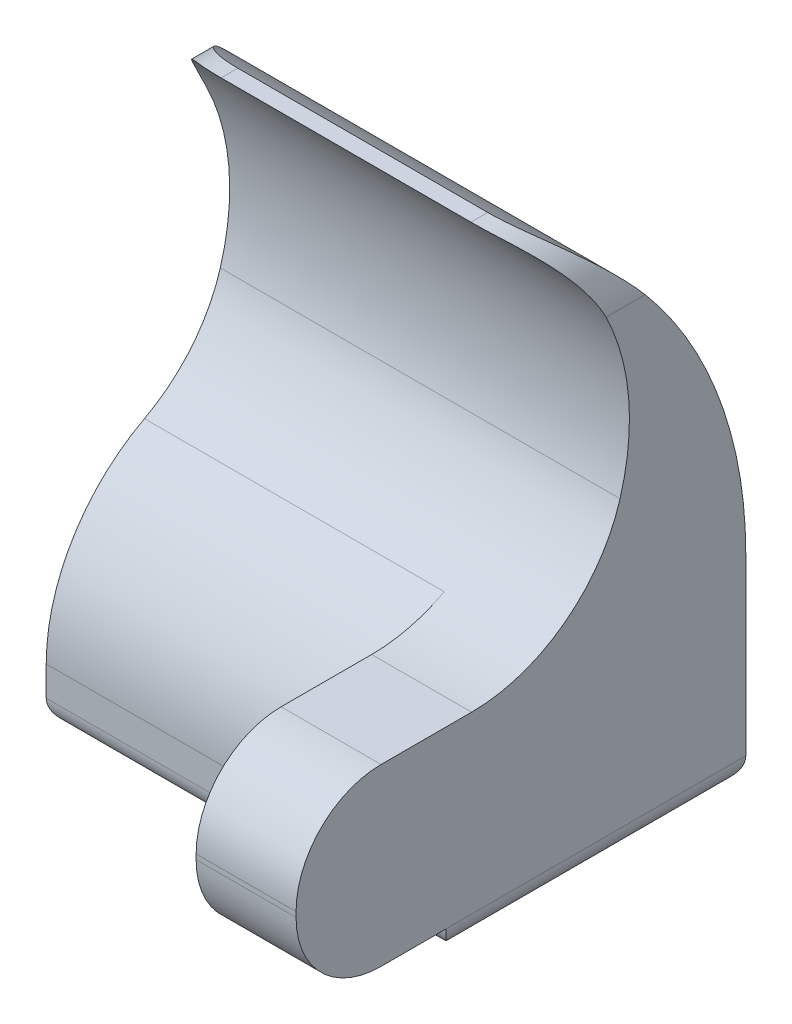
SolidWorks part; units mm, degrees
ref_plane "Front Plane" through (0, 0, 0) normal (0, 0, 1) x (1, 0, 0)
ref_plane "Top Plane" through (0, 0, 0) normal (0, 1, 0) x (1, 0, 0)
ref_plane "Right Plane" through (0, 0, 0) normal (1, 0, 0) x (0, 0, -1)
sketch "Sketch1" plane through (0, 0, 0) normal (0, 1, 0) x (1, 0, 0)
  line L1 (40, 30) -> (-40, 30)
  line L2 (40, 30) -> (40, -30)
  line L3 (40, -30) -> (-40, -30)
  line L4 (-40, 30) -> (-40, -30)
  line L5 (40, 30) -> (-40, -30) construction
  line L6 (40, -30) -> (-40, 30) construction
  point P0 (0, 0)
extrude "Boss-Extrude1" add sketch "Sketch1" along normal blind 40
sketch "Sketch2" plane through (0, 40, 0) normal (0, 1, 0) x (1, 0, 0)
  line L1 (-40, -30) -> (40, -30)
  line L2 (-40, -30) -> (-40, 10)
  line L3 (-40, 10) -> (40, 10)
  line L4 (40, -30) -> (40, 10)
extrude "Boss-Extrude2" add sketch "Sketch2" along normal blind 70
sketch "Sketch3" plane through (40, 0, 0) normal (1, 0, 0) x (0, 0, -1)
  line L1 (10, 40) -> (-30, 40) construction
  line L2 (10, 40) -> (10, 110)
  line L3 (10, 110) -> (-30, 110)
  line L4 (-30, 40) -> (-30, 110)
  arc A0 (10, 40) -> (10, 110) centre (38.2843, 75) cw
  arc A1 (-30, 40) -> (6.6434, 110) centre (55.1823, 40) cw
  line M9 (10, 40) -> (10, 110)
  line M10 (10, 110) -> (-30, 110)
  line M11 (-30, 110) -> (-30, 0)
extrude "Cut-Extrude1" cut sketch "Sketch3" against normal up to next contours M9 M10 M11 | A0 M9 | L2 A0 region at (40, 75, -3.1943) region at (40, 93.341, 19.5782)
fillet "Fillet4" radius 31 1 edges at (0, 40, -10)
fillet "Fillet6" radius 5 4 edges at (0, 0, 30) (40, 0, 0) (0, 0, -30) (-40, 0, 0)
fillet "Fillet7" radius 15 2 edges at (-40, 110, -8.3217) (40, 110, -8.3217)
sketch "Sketch5" plane through (0, 0, -30) normal (0, 0, -1) x (-1, 0, 0)
  line L0 (-40, 40) -> (40, 40) construction
  line L1 (-40, 5) -> (-20, 5)
  line L2 (-40, 5) -> (-40, 40)
  line L3 (-40, 40) -> (-20, 40)
  line L4 (-20, 5) -> (-20, 40)
extrude "Boss-Extrude4" add sketch "Sketch5" along normal blind 30
fillet "Fillet8" radius 17 2 edges at (30, 5, -60) (30, 40, -60)
fillet "Fillet9" radius 37 1 edges at (-10, 40, -30)
sketch "Sketch6" plane through (0, 0, 0) normal (0, -1, 0) x (1, 0, 0)
  line L1 (7.5, 7.5) -> (-7.5, 7.5)
  line L2 (7.5, 7.5) -> (7.5, -7.5)
  line L3 (7.5, -7.5) -> (-7.5, -7.5)
  line L4 (-7.5, 7.5) -> (-7.5, -7.5)
  line L5 (7.5, 7.5) -> (-7.5, -7.5) construction
  line L6 (7.5, -7.5) -> (-7.5, 7.5) construction
  point P0 (0, 0)
extrude "Boss-Extrude5" add sketch "Sketch6" along normal blind 20
fillet "Fillet10" radius 2 4 edges at (-7.5, -10, -7.5) (-7.5, -10, 7.5) (7.5, -10, -7.5) (7.5, -10, 7.5)
mirror "Mirror1" about plane through (40, 40, 30) normal (0, 0, -1) of bodies 106
delete or keep bodies "Body-Delete/Keep 1" type delete bodies bodies 106
